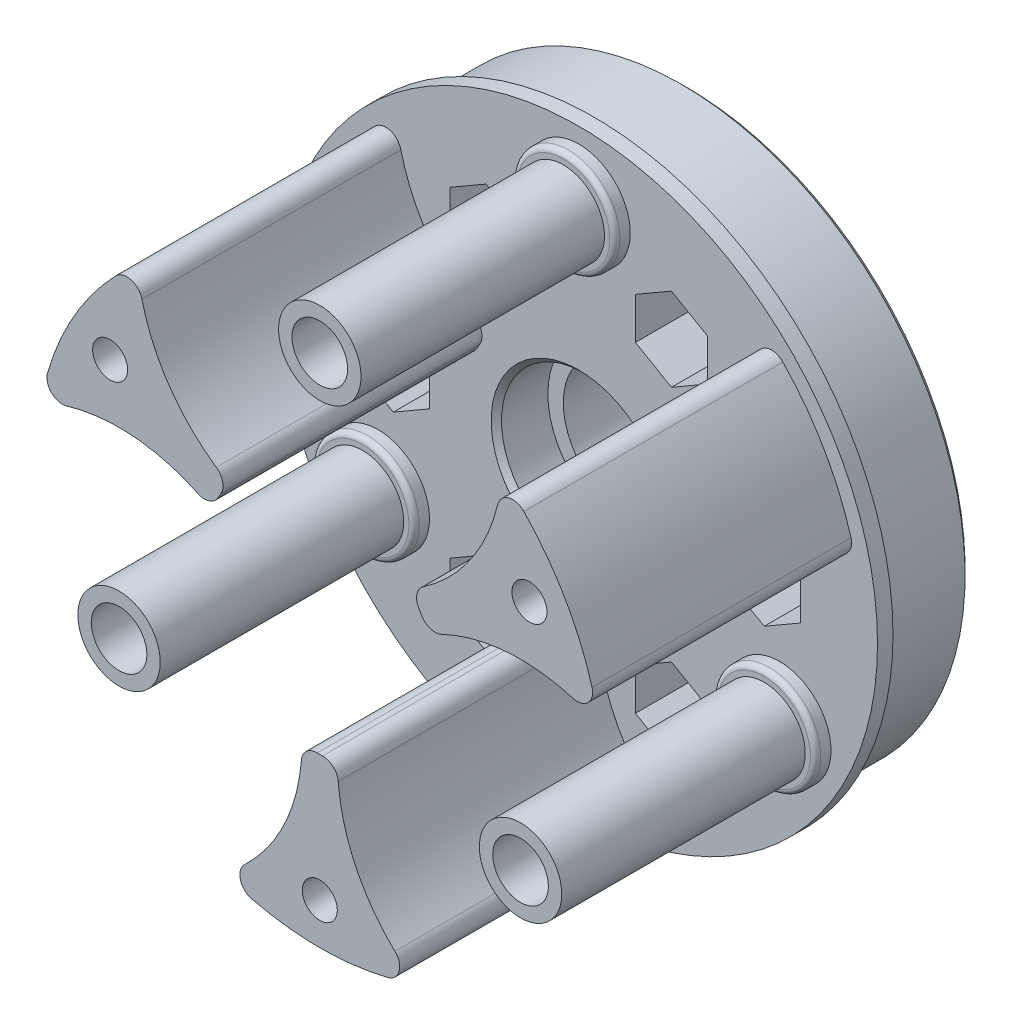
SolidWorks part; units mm, degrees
material "PLA"
ref_plane "Front Plane" through (0, 0, 0) normal (0, 0, 1) x (1, 0, 0)
ref_plane "Top Plane" through (0, 0, 0) normal (0, 1, 0) x (1, 0, 0)
ref_plane "Right Plane" through (0, 0, 0) normal (1, 0, 0) x (0, 0, -1)
sketch "Sketch1" plane through (0, 0, 0) normal (0, 0, 1) x (1, 0, 0)
  circle A0 centre (0, 0) radius 27.5
  circle A1 centre (0, 0) radius 22.5 construction
  circle A2 centre (0, 22.5) radius 2.7
  circle A3 centre (19.4856, -11.25) radius 2.7
  circle A78 centre (-19.4856, -11.25) radius 2.7
  point P15 (0, 0)
  dimension "D1" = 55
  dimension "D2" = 45
  dimension "D3" = 5.4
  dimension "D4" = 3
extrude "Boss-Extrude1" add sketch "Sketch1" along normal blind 10.5
sketch "Sketch2" plane through (0, 0, 10.5) normal (0, 0, 1) x (1, 0, 0)
  circle A0 centre (0, 22.5) radius 4
  circle A2 centre (0, 22.5) radius 2.7 construction
  circle A5 centre (0, 22.5) radius 2.7
  point P15 (0, 0)
  dimension "D1" = 8
extrude "Boss-Extrude2" add sketch "Sketch2" along normal blind 25.1348
sketch "Sketch3" plane through (0, 0, 10.5) normal (0, 0, 1) x (1, 0, 0)
  arc A2 (5, 22.5) -> (5, 22.5) centre (0, 22.5) ccw
  circle A3 centre (0, 22.5) radius 5
  circle M5 centre (0, 22.5) radius 4
extrude "Boss-Extrude3" add sketch "Sketch3" along normal blind 1.5 contours A3 M5
sketch "Sketch4" plane through (0, 0, 10.5) normal (0, 0, 1) x (1, 0, 0)
  line L0 (0, 0) -> (-23.8157, 13.75) construction
  line L1 (0, 0) -> (0, 22.5) construction
  circle A0 centre (0, 0) radius 27.5 construction
  circle A1 centre (0, 0) radius 27.5
  circle A2 centre (0, 22.5) radius 16.25 construction
  circle A6 centre (0, 0) radius 22.5 construction
  arc A8 (-17.691, 21.0542) -> (-8.758, 7.0611) centre (0, 22.5) ccw
  circle A9 centre (0, 0) radius 11.25
  circle A11 centre (0, 0) radius 6.25 construction
  arc A13 (-27.079, 4.7938) -> (-10.4941, 4.0541) centre (-19.4856, -11.25) cw
  circle A16 centre (0, 22.5) radius 17.75 construction
  point P15 (0, 0)
  point P25 (0, 0)
  dimension "D1" = 32.5
  dimension "D5" = 12.5
  dimension "D4" = 5
  dimension "D2" = 60
  dimension "D3" = 1.5
extrude "Boss-Extrude4" add sketch "Sketch4" along normal blind 25.1348 contours A1 A13 A9 A8
fillet "Fillet2" radius 0.5 1 edges at (5, 22.5, 12)
fillet "Fillet5" radius 1.5 4 edges at (-17.691, 21.0542, 23.0674) (-10.4941, 4.0541, 23.0674) (-27.079, 4.7938, 23.0674) (-8.758, 7.0611, 23.0674)
pattern_circular "CirPattern1" count 3 over 360 about axis through (0, 0, 0) along (0, 0, 1) of "Fillet2", "Boss-Extrude4", "Boss-Extrude3", "Boss-Extrude2", "Fillet5"
ref_plane "Plane1" through (0, 0, 35.6348) normal (0, 0, 1) x (1, 0, 0)
sketch "Sketch5" plane through (0, 0, 35.6348) normal (0, 0, 1) x (1, 0, 0)
  line L0 (0, 0) -> (-23.8157, 13.75) construction
  line L1 (0, 0) -> (0, 27.5) construction
  circle A0 centre (0, 0) radius 27.5 construction
  circle A3 centre (-20.3516, 11.75) radius 1.7
  circle A4 centre (0, 0) radius 27.5 construction
  arc A5 (-19.8059, 19.0781) -> (-26.4251, 7.6134) centre (0, 0) ccw construction
  dimension "D2" = 3.4
  dimension "D1" = 4
  dimension "D3" = 60
extrude "Cut-Extrude1" cut sketch "Sketch5" against normal through all
sketch "Sketch6" plane through (0, 0, 0) normal (0, 0, -1) x (-1, 0, 0)
  circle A0 centre (20.3516, 11.75) radius 3.15
  dimension "D1" = 6.3
extrude "Cut-Extrude2" cut sketch "Sketch6" against normal blind 3
sketch "Sketch7" plane through (0, 0, 0) normal (0, 0, -1) x (-1, 0, 0)
  circle A0 centre (0, 22.5) radius 4.65
  circle A1 centre (0, 0) radius 22.5 construction
  point P15 (0, 0)
  dimension "D1" = 9.3
extrude "Cut-Extrude3" cut sketch "Sketch7" against normal blind 5
pattern_circular "CirPattern2" count 3 over 360 about axis through (0, 0, 0) along (0, 0, 1) of "Cut-Extrude3", "Cut-Extrude2", "Cut-Extrude1"
chamfer "Chamfer1" distance 0.5 angle 45 1 edges at (27.5, 0, 0)
sketch "Sketch9" plane through (0, 0, 10.5) normal (0, 0, 1) x (1, 0, 0)
  circle A0 centre (0, 0) radius 8
  dimension "D1" = 16
extrude "Cut-Extrude4" cut sketch "Sketch9" against normal through all
sketch "Sketch10" plane through (0, 0, 0) normal (0, 0, -1) x (-1, 0, 0)
  circle A0 centre (0, 0) radius 8 construction
  circle A1 centre (0, 0) radius 8
  circle A2 centre (0, 0) radius 6.5
  dimension "D1" = 1.5
extrude "Boss-Extrude7" add sketch "Sketch10" against normal blind 5.5
chamfer "Chamfer2" distance 0.5 angle 45 1 edges at (8, 0, 10.5)
sketch "Sketch11" plane through (0, 0, 10.5) normal (0, 0, 1) x (1, 0, 0)
  circle A0 centre (0, 0) radius 27.5
  circle A1 centre (0, 0) radius 29
  dimension "D1" = 1.5
  dimension "D2" = 55
extrude "Boss-Extrude8" add sketch "Sketch11" against normal blind 1.5
sketch "Sketch12" plane through (0, 0, 0) normal (0, 0, -1) x (-1, 0, 0)
  line L0 (0, 0) -> (0, 22.5) construction
  line L1 (0, 0) -> (-20.3516, 11.75) construction
  line L2 (-19.4856, 11.25) -> (0, 22.5) construction
  line L3 (0, 0) -> (-11.25, 19.4856) construction
  circle A0 centre (0, 0) radius 22.5 construction
  circle A1 centre (-9, 15.5885) radius 2.2
  dimension "D1" = 4.4
  dimension "D2" = 4.5
extrude "Cut-Extrude5" cut sketch "Sketch12" against normal through all
sketch "Sketch13" plane through (0, 0, 10.5) normal (0, 0, 1) x (1, 0, 0)
  line L1 (12.5, 13.5677) -> (12.5, 17.6092)
  line L2 (12.5, 17.6092) -> (9, 19.6299)
  line L3 (9, 19.6299) -> (5.5, 17.6092)
  line L4 (5.5, 17.6092) -> (5.5, 13.5677)
  line L5 (5.5, 13.5677) -> (9, 11.547)
  line L6 (9, 11.547) -> (12.5, 13.5677)
  circle A0 centre (9, 15.5885) radius 3.5 construction
  dimension "D1" = 7
extrude "Cut-Extrude6" cut sketch "Sketch13" against normal blind 6
pattern_circular "CirPattern3" count 6 over 360 about axis through (0, 0, 0) along (0, 0, 1) of "Cut-Extrude6", "Cut-Extrude5"
equation "\"Nr\"= 155"
equation "\"module\"= 0.5"
equation "\"pressure_angle\"= 20.0deg"
equation "\"h_a\"= 0.5"
equation "\"h_f\"= 0.625"
equation "\"clr_tip_root\"= 0.125"
equation "\"dp_r\"= 77.5"
equation "\"db_r\"= 72.8261781109079"
equation "\"fw_r\"= 22.13479809822934"
equation "\"alpha_r\"= 0.8539582918412449"
equation "\"beta_r\"= 2.869206906263135"
equation "\"bearing_ID\"= 55"
equation "\"bearing_OD\"= 72"
equation "\"bearing_height\"= 9"
equation "\"clearance_planet\"= 1.5"
equation "\"case_dist\"= 6.5"
equation "\"Motor_case_OD_max\"= 112.3"
equation "\"case_mounting_PCD\"= 104.8"
equation "\"bearing mount thickness\"= 8"
equation "\"case_mounting_hole_dia\"= 3"
equation "\"output_mounting_PCD\"= 80"
equation "\"output_mounting_hole_dia\"= 4"
equation "\"clearance_case_mount_holes_shell_thickness\"= 1"
equation "\"motor_case_OD_base\"= 102.8"
equation "\"sec_carrier_thickness\"= 5"
equation "\"sun_coupler_hub_thickness\"= 4"
equation "\"clearance_sun_coupler_sec_carrier\"= 1.5"
equation "\"clearance_motor_and_case\"= 5"
equation "\"motor_OD\"= 87.8"
equation "\"Motor_case_thickness\"= 2.5"
equation "\"Motor_case_ID\"= 97.8"
equation "\"case_mounting_hole_shift\"= 1.0"
equation "\"output_mounting_nut_wrench_size\"= 7"
equation "\"output_mounting_nut_thickness\"= 3.2"
equation "\"case_mounting_hole_allen_socket_dia\"= 5.5"
equation "\"output_mounting_nut_depth\"= 3"
equation "\"case_mounting_bolt_depth\"= 4.5"
equation "\"Ns\"= 25"
equation "\"Np\"= 65"
equation "\"ring_radial_thickness\"= 5.0"
equation "\"ring_OD\"= 87.5"
equation "\"ring_to_chamfer_clearance\"= 2"
equation "\"Motor_case_OD_base_to_chamfer\"= 5"
equation "\"pattern_offset_from_motor_case_OD_base\"= 3"
equation "\"pattern_bulge_dia\"= 3"
equation "\"pattern_num_bulge\"= 18"
equation "\"pattern_depth\"= 2"
equation "\"motor_height\"= 31.5"
equation "\"case_mounting_wrench_size\"= 5.5"
equation "\"case_mounting_nut_clearance\"= 2"
equation "\"base_plate_thickness\"= 4"
equation "\"case_mounting_nut_thickness\"= 2.4"
equation "\"case_mounting_surface_height\"= 4"
equation "\"motor_mount_hole_PCD\"= 36"
equation "\"motor_mount_hole_dia\"= 4"
equation "\"motor_mount_hole_num\"= 4"
equation "\"central_hole_offset_from_motor_mount_PCD\"= 5"
equation "\"wire_slot_dist_from_center\"= 40"
equation "\"wire_slot_length\"= 10"
equation "\"wire_slot_radius\"= 2.5"
equation "\"driver_upper_holes_dist_from_center\"= 29"
equation "\"driver_lower_holes_dist_from_center\"= 13"
equation "\"driver_side_holes_dist_from_center\"= 22.5"
equation "\"driver_mount_holes_dia\"= 3"
equation "\"driver_mount_inserts_OD\"= 4.8"
equation "\"driver_mount_thickness\"= 1.5"
equation "\"driver_mount_height\"= 6"
equation "\"air_flow_hole_offset\"= 3"
equation "\"num_planet\"= 3"
equation "\"planet_pin_bolt_dia\"= 5"
equation "\"planet_pin_socket_head_dia\"= 8.5"
equation "\"carrier_PCD\"= 45.0"
equation "\"D1@Sketch1\"=\"bearing_ID\""
equation "\"D2@Sketch1\"=\"carrier_PCD\""
equation "\"D3@Sketch1\"=\"planet_pin_bolt_dia\" + \"tight_clearance_3DP\""
equation "\"D4@Sketch1\"=\"num_planet\""
equation "\"D1@Boss-Extrude1\"=\"bearing_height\"+\"carrier_bearing_step_width\""
equation "\"D1@Boss-Extrude2\"=\"fw_p\" + \"clearance_planet\"*2"
equation "\"D1@Boss-Extrude3\"=\"clearance_planet\""
equation "\"D1@Sketch4\"=\"Np\"*\"module\""
equation "\"D3@Sketch4\"=\"clearance_planet\""
equation "\"D1@Boss-Extrude4\"=\"fw_p\"+ \"clearance_planet\" * 2"
equation "\"D1@Fillet2\"=\"clearance_planet\"/3"
equation "\"D1@CirPattern1\"=\"num_planet\""
equation "\"D1@CirPattern2\"=\"num_planet\""
equation "\"D1@Boss-Extrude7\"=\"bearing_height\"+ \"carrier_bearing_step_width\" - \"sun_shaft_bearing_width\""
equation "\"planet_shaft_dia\"= 8"
equation "\"D1@Sketch2\"=\"planet_shaft_dia\""
equation "\"fw_p\"= 22.13479809822934"
equation "\"planet_shaft_step_offset\"= 1"
equation "\"D1@Sketch3\"=\"planet_shaft_step_offset\""
equation "\"carrier_trapezoidal_support_sun_offset\"= 5"
equation "\"D4@Sketch4\"=\"carrier_trapezoidal_support_sun_offset\""
equation "\"carrier_trapezoidal_support_hole_PCD_offset_bearing_ID\"= 4"
equation "\"carrier_trapezoidal_support_hole_dia\"= 3"
equation "\"D2@Sketch5\"=\"carrier_trapezoidal_support_hole_dia\" + \"tight_clearance_3DP\""
equation "\"D1@Cut-Extrude2\"=\"carrier_trapezoidal_support_hole_dia\""
equation "\"carrier_trapezoidal_support_hole_socket_head_dia\"= 5.5"
equation "\"D1@Sketch6\"=\"carrier_trapezoidal_support_hole_socket_head_dia\" + \"loose_clearance_3DP\""
equation "\"D1@Cut-Extrude3\"=\"planet_pin_bolt_dia\""
equation "\"D1@Sketch7\"=\"planet_pin_socket_head_dia\" + \"loose_clearance_3DP\""
equation "\"carrier_bearing_step_width\"= 1.5"
equation "\"standard_clearance_1_5mm\"= 1.5"
equation "\"standard_fillet_1_5mm\"= 1.5"
equation "\"sun_shaft_bearing_OD\"= 16"
equation "\"D1@Sketch9\"=\"sun_shaft_bearing_OD\""
equation "\"D1@Sketch10\"=\"standard_clearance_1_5mm\""
equation "\"sun_shaft_bearing_width\"= 5"
equation "\"standard_bearing_insertion_chamfer\"= 0.5"
equation "\"D1@Chamfer1\"=\"standard_bearing_insertion_chamfer\""
equation "\"D1@Chamfer2\"=\"standard_bearing_insertion_chamfer\""
equation "\"D5@Sketch4\"=\"Ns\"*\"module\""
equation "\"D1@Sketch5\"=\"carrier_trapezoidal_support_hole_PCD_offset_bearing_ID\""
equation "\"D1@Plane1\"=\"fw_p\"+\"clearance_planet\"*2"
equation "\"D1@Sketch11\"=\"standard_clearance_1_5mm\""
equation "\"D2@Sketch11\"=\"bearing_ID\""
equation "\"D1@Boss-Extrude8\"=\"carrier_bearing_step_width\""
equation "\"D2@Sketch4\"=180/\"num_planet\""
equation "\"D3@Sketch5\"=180/\"num_planet\""
equation "\"D7@Sketch2\"=\"carrier_trapezoidal_support_hole_dia\""
equation "\"D5@Sketch2\"= 360 / ( 4 * \"Ns\" ) - \"alpha_s\""
equation "\"D3@Sketch2\"=\"dp_s\"- 2*\"h_b\""
equation "\"D9@Sketch2\"=\"carrier_trapezoidal_support_sun_offset\""
equation "\"carrier_trapezoidal_support_hole_wrench_size\"= 5.5"
equation "\"planet_pin_bolt_wrench_size\"= 8"
equation "\"pressure angle\"= 20.0deg"
equation "\"motor_output_hole_PCD\"= 23"
equation "\"motor_output_hole_dia\"= 4"
equation "\"motor_output_hole_num\"= 4"
equation "\"h_b\"= 0.625"
equation "\"dp_s\"= 12.5"
equation "\"db_s\"= 11.746157759823856"
equation "\"fw_s_calc\"= 22.13479809822934"
equation "\"alpha_s\"= 0.8539582918412449"
equation "\"beta_s\"= 5.49208341631751"
equation "\"dp_p\"= 32.5"
equation "\"db_p\"= 30.540010175542022"
equation "\"alpha_p\"= 0.8539582918412485"
equation "\"beta_p\"= 1.0613141855482722"
equation "\"planet_bearing_OD\"= 12"
equation "\"planet_bearing_width\"= 3.5"
equation "\"planet_bore\"= 10"
equation "\"sun_shaft_bearing_ID\"= 8"
equation "\"sun_hub_dia\"= 33.0"
equation "\"sun_central_bolt_dia\"= 5"
equation "\"sun_central_bolt_socket_head_dia\"= 8.5"
equation "\"fw_s_used\"= 30.13479809822934"
equation "\"motor_output_hole_CSK_OD\"= 8"
equation "\"motor_output_hole_CSK_head_height\"= 2.0"
equation "\"bearing_retainer_thickness\"= 2"
equation "\"tight_clearance_3DP\" = 0.4"
equation "\"loose_clearance_3DP\" = 0.8"
equation "\"D2@Sketch12\"= \"standard_clearance_1_5mm\"*3"
equation "\"D1@Sketch13\"= \"output_mounting_nut_wrench_size\""
equation "\"D1@Cut-Extrude6\"=\"bearing_height\" + \"carrier_bearing_step_width\" - \"standard_clearance_1_5mm\"*3"
equation "\"D1@Sketch12\"= \"output_mounting_hole_dia\" + \"tight_clearance_3DP\""
equation "\"D1@CirPattern3\"= \"num_planet\" * 2"
